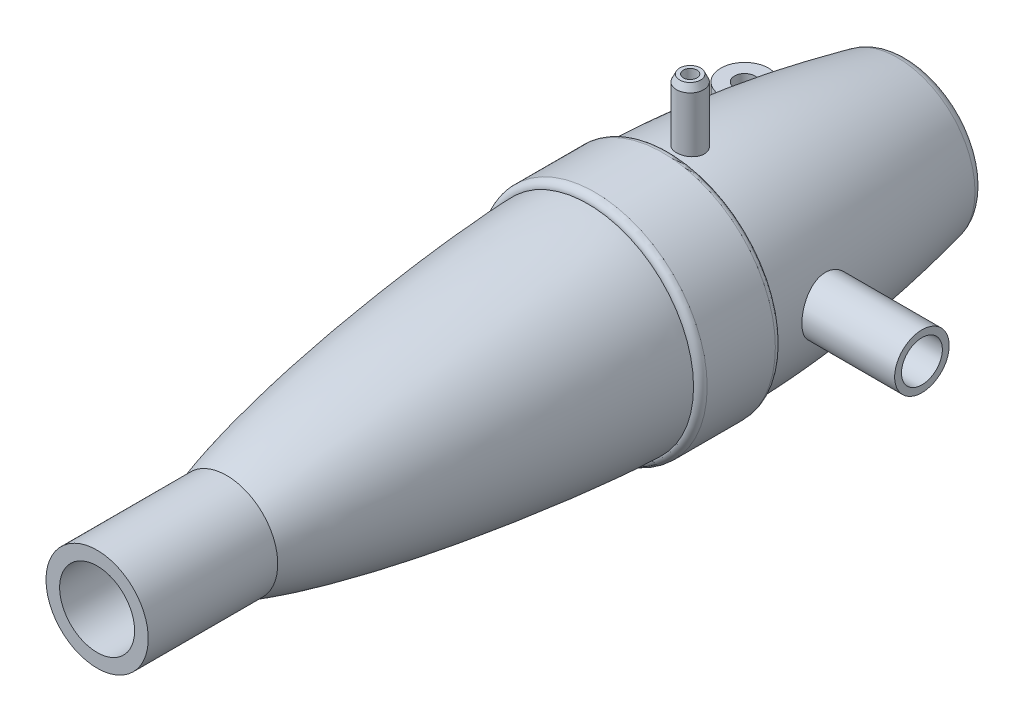
SolidWorks part; units mm, degrees
material "ABS"
ref_plane "Front" through (0, 0, 0) normal (0, 0, 1) x (1, 0, 0)
ref_plane "Top" through (0, 0, 0) normal (0, 1, 0) x (1, 0, 0)
ref_plane "Right" through (0, 0, 0) normal (1, 0, 0) x (0, 0, -1)
sketch "Sketch1" plane through (0, 0, 0) normal (0, 0, 1) x (1, 0, 0)
  circle A0 centre (0, 0) radius 7.5
extrude "Boss-Extrude1" add sketch "Sketch1" along normal blind 19
ref_plane "Plane1" through (0, 0, -53) normal (0, 0, -1) x (-1, 0, 0)
sketch "Sketch2" plane through (0, 0, -53) normal (0, 0, -1) x (-1, 0, 0)
  circle A0 centre (0, 0) radius 15.5
sketch "Sketch3" plane through (0, 0, 0) normal (1, 0, 0) x (0, 0, -1)
  line L0 (53, -15.5) -> (53, 15.5) construction
  line L4 (0, 7.5) -> (0, 5.5)
  line L5 (0, -7.5) -> (0, 7.5) construction
  line L6 (53, 15.5) -> (53, 13.5)
  line L7 (0, 0) -> (53, 0) construction
  spline S0 degree 3 poles (0, 7.5) (17.4166, 13.0157) (46.915, 15.4775) (53, 15.5) knots 0 0 0 0 0.912392 0.912392 0.912392 0.912392
  spline S1 degree 2 poles (0, 5.5) (26.2304, 13.0926) (53, 13.5) knots 0 0 0 0.898157 0.898157 0.898157
revolve "Revolve1" add sketch "Sketch3" angle 360 about L7
sketch "Sketch5" plane through (0, 0, -53) normal (0, 0, -1) x (-1, 0, 0)
  circle A0 centre (0, 0) radius 16.5
  circle A1 centre (0, 0) radius 13.5
extrude "Boss-Extrude3" add sketch "Sketch5" along normal blind 12
sketch "Sketch6" plane through (0, 0, -65) normal (0, 0, -1) x (-1, 0, 0)
  circle A0 centre (0, 0) radius 15.5
ref_plane "Plane2" through (0, 0, -100) normal (0, 0, -1) x (-1, 0, 0)
sketch "Sketch7" plane through (0, 0, -100) normal (0, 0, -1) x (-1, 0, 0)
  circle A0 centre (0, 0) radius 11
sketch "Sketch8" plane through (0, 0, 0) normal (1, 0, 0) x (0, 0, -1)
  line L0 (65, -16.5) -> (65, 16.5) construction
  line L1 (65, -15.5) -> (65, 15.5) construction
  line L2 (100, -11) -> (100, 11) construction
  line L3 (100, -18.15) -> (100, 18.15) construction
  line L7 (65, 15.5) -> (65, 13.5)
  line L8 (100, 11) -> (100, 0)
  line L9 (65, 0) -> (100, 0) construction
  line L10 (100, 0) -> (98, 0)
  line L11 (98, 0) -> (98, 9)
  spline S0 degree 3 poles (65, 15.5) (78.6269, 15.3265) (90.893, 13.1017) (100, 11) knots 0 0 0 0 0.876068 0.876068 0.876068 0.876068
  spline S1 degree 2 poles (65, 13.5) (81.8067, 12.8007) (98, 9) knots 0 0 0 0.795333 0.795333 0.795333
  dimension "D1" = 2
revolve "Revolve2" add sketch "Sketch8" angle 360 about L9
ref_plane "Plane3" through (29, 0, 0) normal (1, 0, 0) x (0, 0, -1)
sketch "Sketch9" plane through (29, 0, 0) normal (1, 0, 0) x (0, 0, -1)
  line L0 (65, -15.5) -> (65, 15.5) construction
  circle A0 centre (73, 0) radius 4
  dimension "D1" = 8
extrude "Boss-Extrude4" add sketch "Sketch9" against normal blind 15
ref_plane "Plane4" through (0, 24.5, 0) normal (0, 1, 0) x (1, 0, 0)
sketch "Sketch10" plane through (0, 24.5, 0) normal (0, 1, 0) x (1, 0, 0)
  line L0 (16.5, 65) -> (-16.5, 65) construction
  circle A0 centre (0, 68) radius 2
  dimension "D1" = 3
extrude "Boss-Extrude5" add sketch "Sketch10" against normal blind 11
sketch "Sketch15" plane through (0, 0, 19) normal (0, 0, 1) x (1, 0, 0)
  circle A0 centre (0, 0) radius 5.5
sketch "Sketch16" plane through (29, 0, 0) normal (1, 0, 0) x (0, 0, -1)
  circle A0 centre (73, 0) radius 3
sketch "Sketch17" plane through (0, 24.5, 0) normal (0, 1, 0) x (1, 0, 0)
  circle A0 centre (0, 68) radius 1
chamfer "Chamfer1" distance 1 angle 25 1 edges at (0, 24.5, -66) first distance on face at (0, 24.5, -66)
fillet "Fillet1" radius 1 2 edges at (-16.5, 0, -53) (-16.5, 0, -65)
fillet "Fillet2" radius 2 1 edges at (11, 0, -100)
extrude "Cut-Extrude1" cut sketch "Sketch15" against normal blind 19 contours A0
extrude "Cut-Extrude2" cut sketch "Sketch17" against normal blind 19 contours A0
extrude "Cut-Extrude3" cut sketch "Sketch16" against normal blind 19 contours A0
sketch "Sketch22" plane through (0, 0, 0) normal (0, 1, 0) x (1, 0, 0)
  line L0 (0, 100) -> (-17, 100) construction
  line L1 (9.403, 100) -> (-9.403, 100) construction
  line L2 (-17, 100) -> (-17, 93) construction
  circle A0 centre (-17, 93) radius 3.5
extrude "Boss-Extrude9" add sketch "Sketch22" along normal blind 2.5 and the other way blind 2.5 separate body
sketch "Sketch23" plane through (0, 0, 0) normal (0, 1, 0) x (1, 0, 0)
  line L0 (-17, 93) -> (-11, 93) construction
  line L2 (-17, 94) -> (-11, 94)
  line L3 (-17, 94) -> (-17, 92)
  line L4 (-17, 92) -> (-11, 92)
  line L5 (-11, 94) -> (-11, 92)
  line L6 (-17, 94) -> (-11, 92) construction
  line L7 (-17, 92) -> (-11, 94) construction
  point P3 (-14, 93)
  dimension "D1" = 2
extrude "Boss-Extrude10" add sketch "Sketch23" along normal blind 2 and the other way blind 2
sketch "Sketch25" plane through (0, 0, 0) normal (0, 1, 0) x (1, 0, 0)
  line L0 (-17, 96.5) -> (-10.6267, 97.6238)
  line L1 (-10.6267, 97.6238) -> (-11.9365, 88.6072)
  line L2 (-11.9365, 88.6072) -> (-17, 89.5)
  line L3 (-17, 89.5) -> (-17, 96.5)
  circle A0 centre (-17, 93) radius 3.5 construction
  dimension "D1" = 80
  dimension "D2" = 80
extrude "Boss-Extrude12" add sketch "Sketch25" along normal blind 1 and the other way blind 1
sketch "Sketch26" plane through (0, 2.5, 0) normal (0, 1, 0) x (1, 0, 0)
  circle A0 centre (-17, 93) radius 1.5
extrude "Cut-Extrude5" cut sketch "Sketch26" against normal through all
